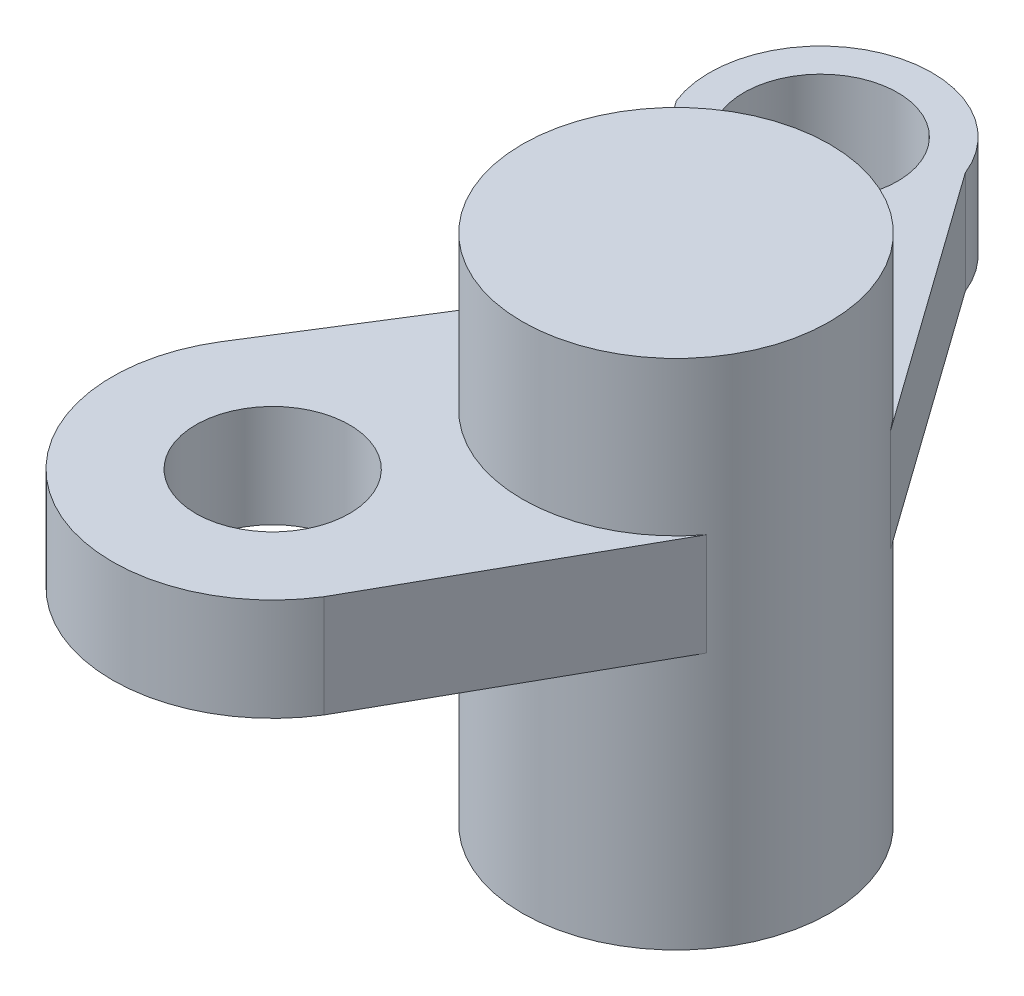
SolidWorks part; units mm, degrees
ref_plane "Front Plane" through (0, 0, 0) normal (0, 0, 1) x (1, 0, 0)
ref_plane "Top Plane" through (0, 0, 0) normal (0, 1, 0) x (1, 0, 0)
ref_plane "Right Plane" through (0, 0, 0) normal (1, 0, 0) x (0, 0, -1)
sketch "Sketch1" plane through (0, 0, 0) normal (0, 1, 0) x (1, 0, 0)
  line L0 (0, -55) -> (0, 55) construction
  line L1 (-55, 0) -> (55, 0) construction
  line L2 (-7.5403, 3.5959) -> (-10.5991, -1.273)
  line L3 (-2.6045, 0.194) -> (-5.2884, -4.5851)
  line L4 (-7.5403, 3.5959) -> (-10.2309, 7.2349)
  line L5 (-2.5578, 3.7423) -> (-6.1925, 8.837)
  circle A0 centre (-5, 2) radius 3
  arc A2 (-10.5991, -1.273) -> (-5.2884, -4.5851) centre (-7.9438, -2.929) ccw
  arc A3 (-10.2309, 7.2349) -> (-6.1925, 8.837) centre (-8.2117, 8.036) cw
  circle A4 centre (-7.9438, -2.929) radius 1.5
  circle A5 centre (-8.2117, 8.036) radius 1.5
  point P16 (-7.5643, -3.0034)
  point P17 (-9.3289, -2.0709)
  point P18 (-8.2117, 8.036)
  dimension "D1" = 6
  dimension "D3" = 3
  dimension "D5" = 3
  dimension "D2" = 5
  dimension "D4" = 2
extrude "Boss-Extrude1" add sketch "Sketch1" along normal blind 10 contours A0 region at (-5, 0, -2)
extrude "Boss-Extrude2" add sketch "Sketch1<3>" along normal blind 2 from offset 5 contours L2 A2 L3 A0 A4 | A3 L4 A0 L5 A5 region at (-6.7754, 0, 0.5759) region at (-7.0554, 0, -6.7049)
sketch "Sketch1<3>" plane through (0, 0, 0) normal (0, 1, 0) x (1, 0, 0) same geometry as "Sketch1"
